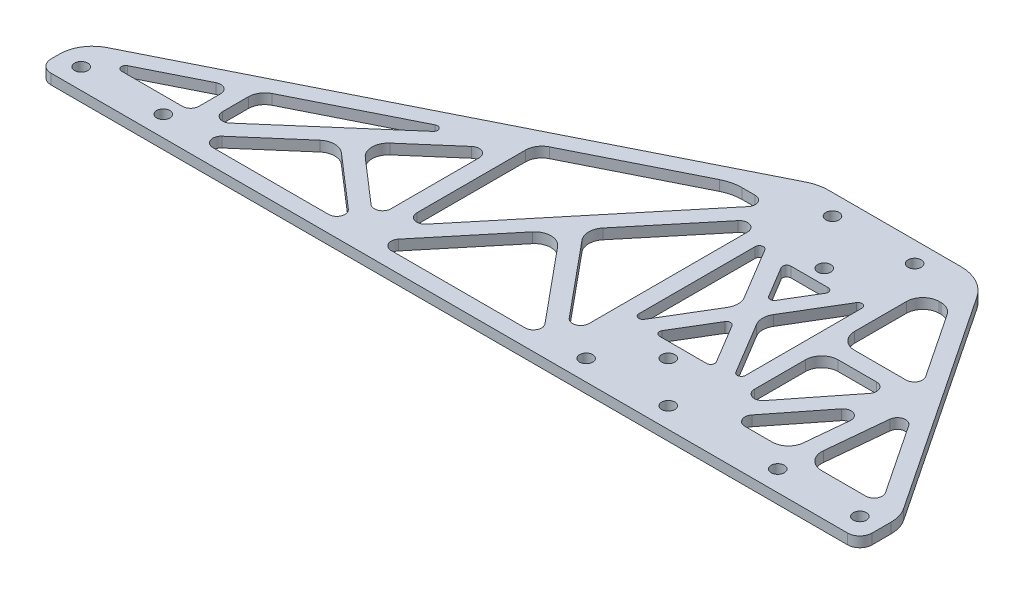
SolidWorks part; units mm, degrees
ref_plane "Front Plane" through (0, 0, 0) normal (0, 0, 1) x (1, 0, 0)
ref_plane "Top Plane" through (0, 0, 0) normal (0, 1, 0) x (1, 0, 0)
ref_plane "Right Plane" through (0, 0, 0) normal (1, 0, 0) x (0, 0, -1)
sketch "Sketch1" plane through (0, 0, 0) normal (0, 1, 0) x (1, 0, 0)
  line L0 (0, 0) -> (254, 0)
  line L2 (203.2, 88.9) -> (152.4, 88.9)
  line L4 (0, 0) -> (0, 12.7)
  line L5 (0, 12.7) -> (152.4, 88.9)
  line L6 (203.2, 88.9) -> (254, 12.7)
  line L7 (254, 12.7) -> (254, 0)
  line L8 (0, 6.35) -> (38.1, 6.35) construction
  line L9 (254, 6.35) -> (222.25, 6.35) construction
  line L10 (139.7, 82.55) -> (207.4333, 82.55) construction
  line L11 (38.1, 0) -> (38.1, 31.75) construction
  line L12 (156.6333, 12.7) -> (154.0933, 7.62)
  line L13 (224.7006, 47.4909) -> (221.314, 12.7) construction
  line L20 (127, 76.2) -> (211.6667, 76.2)
  line L21 (154.0933, 76.2) -> (95.25, 5.08) construction
  line L22 (154.0933, 12.7) -> (154.0933, 7.62)
  line L23 (247.8946, 12.7) -> (194.7333, 12.7)
  line L24 (224.7006, 47.4909) -> (197.2733, 12.7) construction
  line L28 (224.7006, 47.4909) -> (194.7333, 47.4909) construction
  line L31 (5.08, 9.5604) -> (153.5992, 83.82)
  line L32 (200.4813, 83.82) -> (153.5992, 83.82)
  line L33 (200.4813, 83.82) -> (248.92, 11.1619)
  line L34 (248.92, 11.1619) -> (248.92, 5.08)
  line L35 (5.08, 5.08) -> (248.92, 5.08)
  line L36 (5.08, 5.08) -> (5.08, 9.5604)
  line L37 (95.25, 5.08) -> (95.25, 54.6454) construction
  line L39 (124.6717, 40.64) -> (154.0933, 5.08) construction
  line L40 (95.25, 54.6454) -> (38.1, 5.08) construction
  line L41 (66.675, 29.8627) -> (95.25, 5.08) construction
  line L42 (154.0933, 7.62) -> (154.0933, 5.08)
  line L83 (152.8233, 5.08) -> (150.2833, 0)
  line L84 (122.7147, 39.0208) -> (152.1363, 3.4608)
  line L107 (152.1363, 77.8192) -> (93.293, 6.6992)
  line L108 (156.6333, 76.2) -> (194.7333, 12.7) construction
  line L113 (194.7333, 76.2) -> (156.6333, 12.7) construction
  line L117 (97.79, 5.08) -> (97.79, 60.2105)
  line L118 (156.6333, 12.7) -> (194.7333, 12.7)
  line L119 (194.7333, 12.7) -> (201.0833, 0)
  line L120 (154.0933, 6.35) -> (197.9083, 6.35) construction
  line L126 (192.5553, 77.5068) -> (154.4553, 14.0068)
  line L127 (154.4553, 74.8932) -> (192.5553, 11.3932)
  line L128 (156.6333, 12.7) -> (156.6333, 76.2) construction
  line L129 (194.7333, 12.7) -> (194.7333, 76.2) construction
  line L130 (197.2733, 12.7) -> (197.2733, 76.2)
  line L131 (159.1733, 12.7) -> (159.1733, 76.2)
  line L132 (192.1933, 12.7) -> (192.1933, 76.2)
  line L133 (154.0933, 12.7) -> (154.0933, 76.2)
  line L147 (196.9114, 74.8932) -> (158.8114, 11.3932)
  line L148 (158.8114, 77.5068) -> (196.9114, 14.0068)
  line L154 (97.79, 60.2105) -> (36.4358, 6.9989)
  line L155 (65.0108, 27.9438) -> (93.5858, 3.1611)
  line L156 (224.7006, 50.0309) -> (194.7333, 50.0309)
  line L157 (222.7059, 49.0635) -> (195.2786, 14.2725)
  line L158 (197.2733, 12.7) -> (197.2733, 7.62)
  line L159 (222.1726, 47.737) -> (218.7859, 12.9461)
  line L160 (126.6287, 42.2592) -> (156.0503, 6.6992)
  line L163 (156.0503, 74.5808) -> (97.207, 3.4608)
  line L164 (92.71, 5.08) -> (92.71, 49.0803)
  line L165 (92.71, 49.0803) -> (39.7642, 3.1611)
  line L166 (175.6833, 19.05) -> (162.9833, 6.35) construction
  line L167 (175.6833, 19.05) -> (188.3833, 6.35) construction
  line L168 (162.9833, 82.55) -> (175.6833, 67.31) construction
  line L169 (175.6833, 67.31) -> (188.3833, 82.55) construction
  line L170 (161.6625, 21.082) -> (189.7041, 21.082) construction
  line L171 (161.6625, 23.622) -> (189.7041, 23.622)
  line L172 (163.1865, 65.278) -> (188.1801, 65.278) construction
  line L173 (163.1865, 62.738) -> (188.1801, 62.738)
  line L174 (68.3392, 31.7816) -> (96.9142, 6.9989)
  line L175 (224.7006, 44.9509) -> (194.7333, 44.9509)
  line L176 (226.6953, 45.9184) -> (199.268, 11.1275)
  line L177 (227.2287, 47.2449) -> (223.842, 12.4539)
  line L178 (8.8192, 11.43) -> (38.1, 11.43)
  line L179 (40.64, 0) -> (40.64, 31.75)
  line L180 (35.56, 0) -> (35.56, 31.75)
  circle A0 centre (6.7733, 6.35) radius 2.032
  circle A1 centre (32.1733, 6.35) radius 2.032
  circle A2 centre (222.25, 6.35) radius 2.032
  circle A3 centre (247.65, 6.35) radius 2.032
  circle A4 centre (162.9833, 82.55) radius 2.032
  circle A5 centre (188.3833, 82.55) radius 2.032
  circle A28 centre (162.9833, 6.35) radius 2.032
  circle A29 centre (188.3833, 6.35) radius 2.032
  arc A32 (197.2733, 12.7) -> (192.1933, 12.7) centre (194.7333, 12.7) cw
  arc A33 (197.2733, 76.2) -> (192.1933, 76.2) centre (194.7333, 76.2) ccw
  arc A34 (159.1733, 12.7) -> (154.0933, 12.7) centre (156.6333, 12.7) cw
  arc A35 (159.1733, 76.2) -> (154.0933, 76.2) centre (156.6333, 76.2) ccw
  arc A45 (192.5553, 77.5068) -> (196.9114, 74.8932) centre (194.7333, 76.2) cw
  arc A46 (154.4553, 14.0068) -> (158.8114, 11.3932) centre (156.6333, 12.7) ccw
  arc A47 (154.4553, 74.8932) -> (158.8114, 77.5068) centre (156.6333, 76.2) cw
  arc A48 (192.5553, 11.3932) -> (196.9114, 14.0068) centre (194.7333, 12.7) ccw
  circle A59 centre (175.6833, 19.05) radius 2.032
  circle A60 centre (175.6833, 67.31) radius 2.032
  arc A61 (122.7147, 39.0208) -> (126.6287, 42.2592) centre (124.6717, 40.64) cw
  arc A62 (152.1363, 3.4608) -> (156.0503, 6.6992) centre (154.0933, 5.08) ccw
  arc A63 (152.1363, 77.8192) -> (156.0503, 74.5808) centre (154.0933, 76.2) cw
  arc A64 (93.293, 6.6992) -> (97.207, 3.4608) centre (95.25, 5.08) ccw
  arc A65 (97.79, 5.08) -> (92.71, 5.08) centre (95.25, 5.08) cw
  arc A66 (36.4358, 6.9989) -> (39.7642, 3.1611) centre (38.1, 5.08) ccw
  arc A67 (65.0108, 27.9438) -> (68.3392, 31.7816) centre (66.675, 29.8627) cw
  arc A68 (93.5858, 3.1611) -> (96.9142, 6.9989) centre (95.25, 5.08) ccw
  arc A69 (224.7006, 50.0309) -> (224.7006, 44.9509) centre (224.7006, 47.4909) cw
  arc A70 (194.7333, 50.0309) -> (194.7333, 44.9509) centre (194.7333, 47.4909) ccw
  arc A71 (222.7059, 49.0635) -> (226.6953, 45.9184) centre (224.7006, 47.4909) cw
  arc A72 (195.2786, 14.2725) -> (199.268, 11.1275) centre (197.2733, 12.7) ccw
  arc A73 (222.1726, 47.737) -> (227.2287, 47.2449) centre (224.7006, 47.4909) cw
  arc A74 (218.7859, 12.9461) -> (223.842, 12.4539) centre (221.314, 12.7) ccw
  arc A75 (40.64, 0) -> (35.56, 0) centre (38.1, 0) cw
  arc A76 (40.64, 31.75) -> (35.56, 31.75) centre (38.1, 31.75) ccw
  dimension "D7" = 4.064
  dimension "D8" = 25.4
  dimension "D9" = 130.81
  dimension "D10" = 25.4
  dimension "D11" = 6.35
  dimension "D13" = 19.05
  dimension "D1" = 254
  dimension "D2" = 50.8
  dimension "D3" = 88.9
  dimension "D4" = 152.4
  dimension "D5" = 12.7
  dimension "D6" = 6.35
  dimension "D12" = 25.4
  dimension "D14" = 38.1
  dimension "D15" = 12.7
  dimension "D16" = 57.15
  dimension "D18" = 12.7
  dimension "D19" = 2.54
  dimension "D20" = 50.8
  dimension "D21" = 25.4
  dimension "D22" = 2.54
  dimension "D23" = 6.35
  dimension "D24" = 2.54
  dimension "D29" = 6.35
  dimension "D30" = 38.1
  dimension "D31" = 25.4
  dimension "D32" = 6.35
  dimension "D33" = 2.54
  dimension "D36" = 12.7
  dimension "D38" = 15.24
  dimension "D39" = 2.54
  dimension "D40" = 2.54
  dimension "D17" = 5.08
  dimension "D25" = 2.54
  dimension "D26" = 2.54
  dimension "D37" = 2.54
extrude "Boss-Extrude1" add sketch "Sketch1" along normal blind 3.175 contours L0 L7 L6 L2 L5 L4 | A0 | A1 | A5 | A4 | A2 | A3
extrude "Cut-Extrude2" cut sketch "Sketch1<3>" along normal through all contours L154 L31 L11 | L155 L165 L35 | L165 L174 L164 | L117 L107 L20 L31 | L84 L163 L35 | L133 L163 L160 L22 | L157 L175 L130 | L156 L33 L20 L130 | L147 L148 L132 | L131 L126 L127 | L173 L148 L126 | L147 L171 L127 | A74 L159 L176 L23 | L33 L177 L23 | L178 L180 L31 | A28 | A59 | A29 | A60 region at (26.6464, 0, -15.8868) region at (66.675, 0, -12.2202) region at (55.7919, 0, -29.3513) region at (124.6717, 0, -15.6052) region at (116.7849, 0, -50.1772) region at (85.3239, 0, -29.8627) region at (145.385, 0, -40.64) region at (206.5243, 0, -60.8789) region at (213.5344, 0, -21.5056) region at (204.6702, 0, -35.5682) region at (175.6833, 0, -28.919) region at (187.6774, 0, -44.45) region at (163.6893, 0, -44.45) region at (232.896, 0, -23.1836) region at (175.6833, 0, -58.2876)
sketch "Sketch1<3>" plane through (0, 0, 0) normal (0, 1, 0) x (1, 0, 0) same geometry as "Sketch1"
fillet "Fillet1" radius 3.81 2 edges at (254, 1.5875, 0) (0, 1.5875, 0)
fillet "Fillet2" radius 10.16 2 edges at (254, 1.5875, -12.7) (0, 1.5875, -12.7)
fillet "Fillet3" radius 12.7 2 edges at (203.2, 1.5875, -88.9) (152.4, 1.5875, -88.9)
fillet "Fillet4" radius 1.27 12 edges at (159.1733, 1.5875, -67.0298) (192.1933, 1.5875, -67.0298) (192.1933, 1.5875, -21.8702) (159.1733, 1.5875, -21.8702) (183.694, 1.5875, -62.738) (167.6727, 1.5875, -62.738) (175.6833, 1.5875, -49.3869) (185.218, 1.5875, -23.622) (166.1487, 1.5875, -23.622) (175.6833, 1.5875, -39.5131) (86.0958, 1.5875, -50.0683) (8.8192, 1.5875, -11.43)
fillet "Fillet5" radius 2.54 20 edges at (223.0073, 1.5875, -50.0309) (247.8946, 1.5875, -12.7) (226.9275, 1.5875, -44.1507) (221.3335, 1.5875, -39.1171) (200.5077, 1.5875, -12.7) (197.2733, 1.5875, -16.8027) (219.4639, 1.5875, -44.9509) (97.79, 1.5875, -12.1344) (92.71, 1.5875, -49.0803) (41.9767, 1.5875, -5.08) (91.3733, 1.5875, -5.08) (92.71, 1.5875, -10.6451) (98.5467, 1.5875, -5.08) (150.7967, 1.5875, -5.08) (154.0933, 1.5875, -9.0645) (154.0933, 1.5875, -72.2155) (150.7967, 1.5875, -76.2) (35.56, 1.5875, -24.8004) (35.56, 1.5875, -11.43) (40.64, 1.5875, -10.6451)
fillet "Fillet6" radius 5.08 14 edges at (172.7212, 1.5875, -44.45) (178.6455, 1.5875, -44.45) (223.866, 1.5875, -12.7) (218.774, 1.5875, -12.7) (197.2733, 1.5875, -50.0309) (197.2733, 1.5875, -44.9509) (197.2733, 1.5875, -76.2) (205.5613, 1.5875, -76.2) (66.675, 1.5875, -26.5005) (70.5517, 1.5875, -29.8627) (97.79, 1.5875, -55.9154) (127.9683, 1.5875, -40.64) (124.6717, 1.5875, -36.6555) (40.64, 1.5875, -27.3404)
fillet "Fillet7" radius 12.7 1 edges at (138.3592, 1.5875, -76.2)
